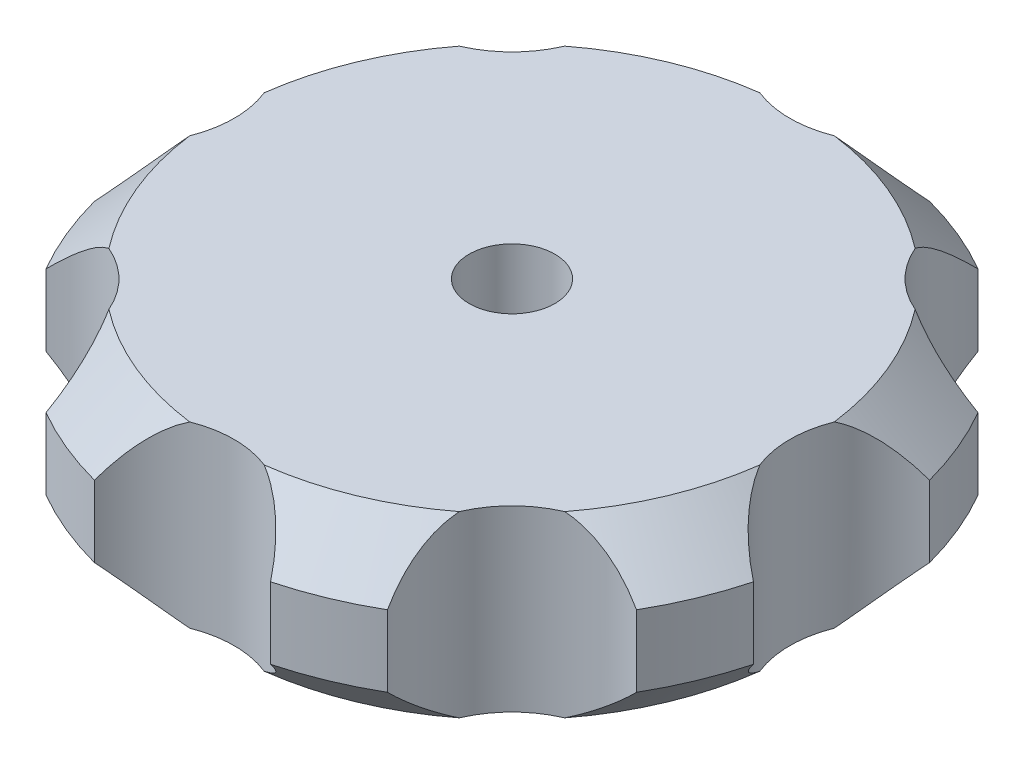
SolidWorks part; units mm, degrees
ref_plane "Front Plane" through (0, 0, 0) normal (0, 0, 1) x (1, 0, 0)
ref_plane "Top Plane" through (0, 0, 0) normal (0, 1, 0) x (1, 0, 0)
ref_plane "Right Plane" through (0, 0, 0) normal (1, 0, 0) x (0, 0, -1)
sketch "Sketch1" plane through (0, 0, 0) normal (0, 1, 0) x (1, 0, 0)
  line L0 (0, -21.2055) -> (21.2055, -21.2055) construction
  line L1 (0, -21.2055) -> (14.9946, -14.9946) construction
  line L2 (14.9946, -14.9946) -> (21.2055, 0) construction
  line L3 (21.2055, 0) -> (14.9946, 14.9946) construction
  line L4 (14.9946, 14.9946) -> (0, 21.2055) construction
  line L5 (0, 21.2055) -> (-14.9946, 14.9946) construction
  line L6 (-14.9946, 14.9946) -> (-21.2055, 0) construction
  line L7 (-21.2055, 0) -> (-14.9946, -14.9946) construction
  line L8 (-14.9946, -14.9946) -> (0, -21.2055) construction
  line L9 (21.2055, -21.2055) -> (21.2055, 0) construction
  arc A1 (4.9292, -18.444) -> (-4.9292, -18.444) centre (0, -21.2055) ccw
  arc A2 (-9.5565, -16.5274) -> (-16.5274, -9.5565) centre (-14.9946, -14.9946) ccw
  arc A3 (-18.444, -4.9292) -> (-18.444, 4.9292) centre (-21.2055, 0) ccw
  arc A4 (-16.5274, 9.5565) -> (-9.5565, 16.5274) centre (-14.9946, 14.9946) ccw
  arc A5 (-4.9292, 18.444) -> (4.9292, 18.444) centre (0, 21.2055) ccw
  arc A6 (9.5565, 16.5274) -> (16.5274, 9.5565) centre (14.9946, 14.9946) ccw
  arc A7 (-9.5565, -16.5274) -> (-4.9292, -18.444) centre (0, 0) ccw
  arc A8 (-16.5274, -9.5565) -> (-18.444, -4.9292) centre (0, 0) cw
  arc A9 (-18.444, 4.9292) -> (-16.5274, 9.5565) centre (0, 0) cw
  arc A10 (-9.5565, 16.5274) -> (-4.9292, 18.444) centre (0, 0) cw
  arc A11 (4.9292, 18.444) -> (9.5565, 16.5274) centre (0, 0) cw
  arc A13 (18.444, 4.9292) -> (18.444, -4.9292) centre (21.2055, 0) ccw
  arc A14 (16.5274, -9.5565) -> (9.5565, -16.5274) centre (14.9946, -14.9946) ccw
  arc A15 (4.9292, -18.444) -> (9.5565, -16.5274) centre (0, 0) ccw
  arc A16 (16.5274, -9.5565) -> (18.444, -4.9292) centre (0, 0) ccw
  arc A17 (18.444, 4.9292) -> (16.5274, 9.5565) centre (0, 0) ccw
  circle A18 centre (0, 0) radius 19.5913 construction
  point P23 (0, 0)
  point P27 (-4.9292, -18.444)
  point P29 (-4.9292, -18.444)
  point P31 (-7.3059, -17.6381)
  point P33 (-7.4973, -18.1)
  point P37 (-9.5565, -16.5274)
  dimension "D1" = 16.23
  dimension "D2" = 0.5
  dimension "D3" = 5.65
  dimension "D4" = 8
extrude "Boss-Extrude1" add sketch "Sketch1" along normal blind 10
chamfer "Chamfer1" distance 3 angle 45 16 edges at (-7.3059, 0, -17.6381) (7.3059, 0, -17.6381) (17.6381, 0, -7.3059) (17.6381, 0, 7.3059) (7.3059, 0, 17.6381) (-7.3059, 0, 17.6381) (-17.6381, 0, 7.3059) (-17.6381, 0, -7.3059) (-17.6381, 10, -7.3059) (-7.3059, 10, -17.6381) (7.3059, 10, -17.6381) (17.6381, 10, -7.3059) (17.6381, 10, 7.3059) (7.3059, 10, 17.6381) (-7.3059, 10, 17.6381) (-17.6381, 10, 7.3059)
sketch "Sketch2" plane through (0, 10, 0) normal (0, 1, 0) x (1, 0, 0)
  point P0 (0, 0)
hole_wizard "M4 Clearance Hole1" positions "Sketch2" profile "Sketch3" hole size "M4" standard "ANSI Metric" end condition through all
sketch "Sketch3" plane through (0, 10, 0) normal (1, 0, 0) x (0, 0, 1)
  line L0 (0, 0) -> (0, 10)
  line L1 (0, 10) -> (2.4, 10)
  line L2 (2.4, 10) -> (2.4, 0)
  line L5 (2.4, 0) -> (0, 0)
  line L11 (0, -6.35) -> (0, 107.95) construction
  dimension "Thru Hole Dia." = 4.8
  dimension "Thru Hole Depth" = 10
